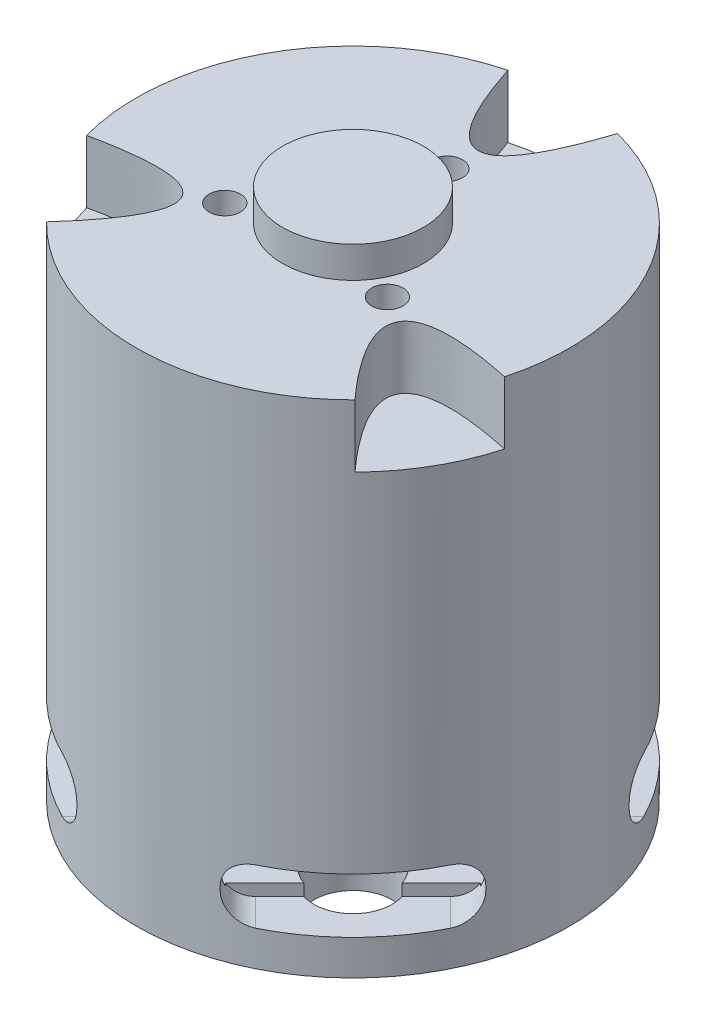
SolidWorks part; units mm, degrees
ref_plane "Front" through (0, 0, 0) normal (0, 0, 1) x (1, 0, 0)
ref_plane "Top" through (0, 0, 0) normal (0, 1, 0) x (1, 0, 0)
ref_plane "Right" through (0, 0, 0) normal (1, 0, 0) x (0, 0, -1)
sketch "Sketch1" plane through (0, 0, 0) normal (0, 1, 0) x (1, 0, 0)
  line L0 (0, 13.85) -> (0, -13.85) construction
  line L1 (-13.85, 0) -> (13.85, 0) construction
  line L2 (0, 0) -> (-13.4345, 13.4345) construction
  circle A0 centre (0, 0) radius 13.85
  circle A1 centre (0, 8) radius 1.5
  circle A2 centre (-9.5, 0) radius 1.5
  circle A3 centre (-6.7175, 6.7175) radius 2.5
  circle A4 centre (6.7175, 6.7175) radius 2.5
  circle A5 centre (9.5, 0) radius 1.5
  circle A6 centre (6.7175, -6.7175) radius 2.5
  circle A7 centre (0, -8) radius 1.5
  circle A8 centre (-6.7175, -6.7175) radius 2.5
  dimension "D1" = 27.7
  dimension "D2" = 3
  dimension "D3" = 3
  dimension "D6" = 5
  dimension "D4" = 9.5
  dimension "D5" = 8
  dimension "D7" = 9.5
extrude "Boss-Extrude1" add sketch "Sketch1" along normal blind 3
sketch "Sketch2" plane through (0, 3, 0) normal (0, 1, 0) x (1, 0, 0)
  circle A0 centre (0, 0) radius 12.35
  circle A1 centre (0, 0) radius 13.85
  circle A2 centre (0, 0) radius 13.85
  dimension "D1" = 0
  dimension "D2" = 1.5
extrude "Boss-Extrude2" add sketch "Sketch2" along normal blind 4
ref_plane "Plane1" through (-9.7934, 0, 9.7934) normal (-0.7071, 0, 0.7071) x (0, -1, 0)
sketch "Sketch3" plane through (-9.7934, 0, 9.7934) normal (-0.7071, 0, 0.7071) x (0, -1, 0)
  line L0 (0, 0) -> (-7, 0) construction
  line L1 (-7, 13.85) -> (-7, -13.85) construction
  line L2 (0, -13.85) -> (0, 13.85) construction
  line L3 (-4.15, 6) -> (-3.85, 6)
  line L4 (-5.75, 4.4) -> (-5.75, -4.4)
  line L5 (-4.15, -6) -> (-3.85, -6)
  line L6 (-2.25, 4.4) -> (-2.25, -4.4)
  line L7 (-5.75, 6) -> (-2.25, -6) construction
  line L8 (-5.75, -6) -> (-2.25, 6) construction
  arc A0 (-3.85, 6) -> (-2.25, 4.4) centre (-3.85, 4.4) cw
  arc A1 (-4.15, 6) -> (-5.75, 4.4) centre (-4.15, 4.4) ccw
  arc A2 (-2.25, -4.4) -> (-3.85, -6) centre (-3.85, -4.4) cw
  arc A3 (-4.15, -6) -> (-5.75, -4.4) centre (-4.15, -4.4) cw
  point P5 (-4, 0)
  dimension "D4" = 1.6
  dimension "D1" = 4
  dimension "D2" = 3.5
  dimension "D3" = 12
extrude "Cut-Extrude1" cut sketch "Sketch3" against normal blind 3.2
ref_axis "Axis1" through (0, 7, 0) along (0, -1, 0)
pattern_circular "CirPattern1" count 4 over 360 about axis through (0, 7, 0) along (0, -1, 0) of "Cut-Extrude1"
sketch "Sketch4" plane through (0, 7, 0) normal (0, 1, 0) x (1, 0, 0)
  circle A1 centre (0, 0) radius 13.85
  circle A2 centre (0, 0) radius 13.85
  dimension "D1" = 0
extrude "Boss-Extrude3" add sketch "Sketch4" along normal blind 25
sketch "Sketch5" plane through (0, 32, 0) normal (0, 1, 0) x (1, 0, 0)
  line L0 (0, 0) -> (0, 13.85) construction
  circle A0 centre (0, 0) radius 13.85 construction
  circle A1 centre (0, 6) radius 1
  circle A2 centre (5.1962, -3) radius 1
  circle A3 centre (-5.1962, -3) radius 1
  arc A4 (-13.3551, -3.6691) -> (-9.8551, -9.7313) centre (0, 0) ccw
  arc A5 (3.5, 13.4005) -> (-3.5, 13.4005) centre (0, 0) ccw
  arc A6 (9.8551, -9.7313) -> (13.3551, -3.6691) centre (0, 0) ccw
  spline S0 degree 2 poles (-3.5, 13.4005) (0, 2.5995) (3.5, 13.4005) knots 0 0 0 1 1 1
  spline S1 degree 2 poles (13.3551, -3.6691) (2.2513, -1.2998) (9.8551, -9.7313) knots 0 0 0 1 1 1
  spline S2 degree 2 poles (-9.8551, -9.7313) (-2.2513, -1.2998) (-13.3551, -3.6691) knots 0 0 0 1 1 1
  point P26 (0, 0)
  dimension "D1" = 2
  dimension "D2" = 6
  dimension "D3" = 3.5
  dimension "D4" = 3.5
  dimension "D5" = 2
  dimension "D6" = 3
extrude "Cut-Extrude2" cut sketch "Sketch5" against normal blind 4
sketch "Sketch6" plane through (0, 32, 0) normal (0, 1, 0) x (1, 0, 0)
  circle A0 centre (0, 0) radius 4.5
  dimension "D1" = 9
extrude "Boss-Extrude4" add sketch "Sketch6" along normal blind 2
sketch "Sketch7" plane through (0, 0, 0) normal (0, -1, 0) x (1, 0, 0)
  circle A0 centre (0, 0) radius 1.585
  dimension "D1" = 3.17
extrude "Boss-Extrude5" add sketch "Sketch7" along normal blind 2
